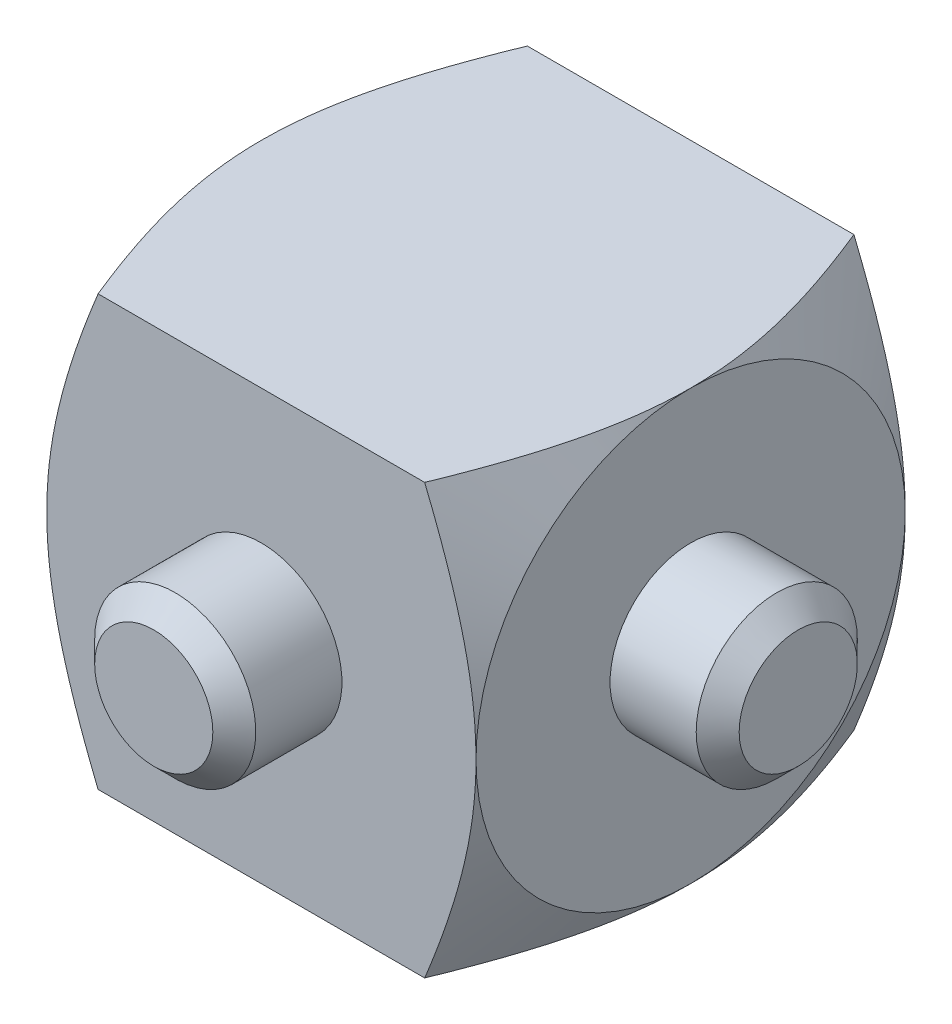
SolidWorks part; units mm, degrees
ref_plane "Front Plane" through (0, 0, 0) normal (0, 0, 1) x (1, 0, 0)
ref_plane "Top Plane" through (0, 0, 0) normal (0, 1, 0) x (1, 0, 0)
ref_plane "Right Plane" through (0, 0, 0) normal (1, 0, 0) x (0, 0, -1)
sketch "Sketch1" plane through (0, 0, 0) normal (0, 0, 1) x (1, 0, 0)
  line L1 (-12.6873, -12.6873) -> (12.6873, -12.6873)
  line L2 (-12.6873, -12.6873) -> (-12.6873, 12.6873)
  line L3 (-12.6873, 12.6873) -> (12.6873, 12.6873)
  line L4 (12.6873, -12.6873) -> (12.6873, 12.6873)
  line L5 (-12.6873, -12.6873) -> (12.6873, 12.6873) construction
  line L6 (-12.6873, 12.6873) -> (12.6873, -12.6873) construction
  point P0 (0, 0)
  dimension "D1" = 25.3746
  dimension "D2" = 25.3746
extrude "Boss-Extrude1" add sketch "Sketch1" along normal mid plane 25.3746
sketch "Sketch2" plane through (12.6873, 0, 0) normal (1, 0, 0) x (0, 0, -1)
  circle A0 centre (0, 0) radius 12.6873
extrude "Cut-Extrude1" cut sketch "Sketch2" against normal through all draft 60 flip side to cut
mirror "Mirror1" about plane through (0, 0, 0) normal (1, 0, 0) of "Cut-Extrude1"
sketch "Sketch3" plane through (0, 0, 0) normal (0, 0, 1) x (1, 0, 0)
  circle A0 centre (0, 0) radius 4.7625
extrude "Cut-Extrude2" cut sketch "Sketch3" against normal through all and the other way through all
extrude "Boss-Extrude3" add sketch "Sketch3<2>" along normal mid plane 38.1
sketch "Sketch3<2>" plane through (0, 0, 0) normal (0, 0, 1) x (1, 0, 0) same geometry as "Sketch3"
ref_plane "Plane1" through (0, 0, 0) normal (-0.7071, 0, -0.7071) x (-0.7071, 0, 0.7071)
mirror "Mirror2" about plane through (0, 0, 0) normal (-0.7071, 0, -0.7071) of "Boss-Extrude3"
chamfer "Chamfer6" distance 1.27 angle 45 4 edges at (4.7625, 0, -19.05) (-19.05, 0, -4.7625) (19.05, 0, -4.7625) (4.7625, 0, 19.05)
